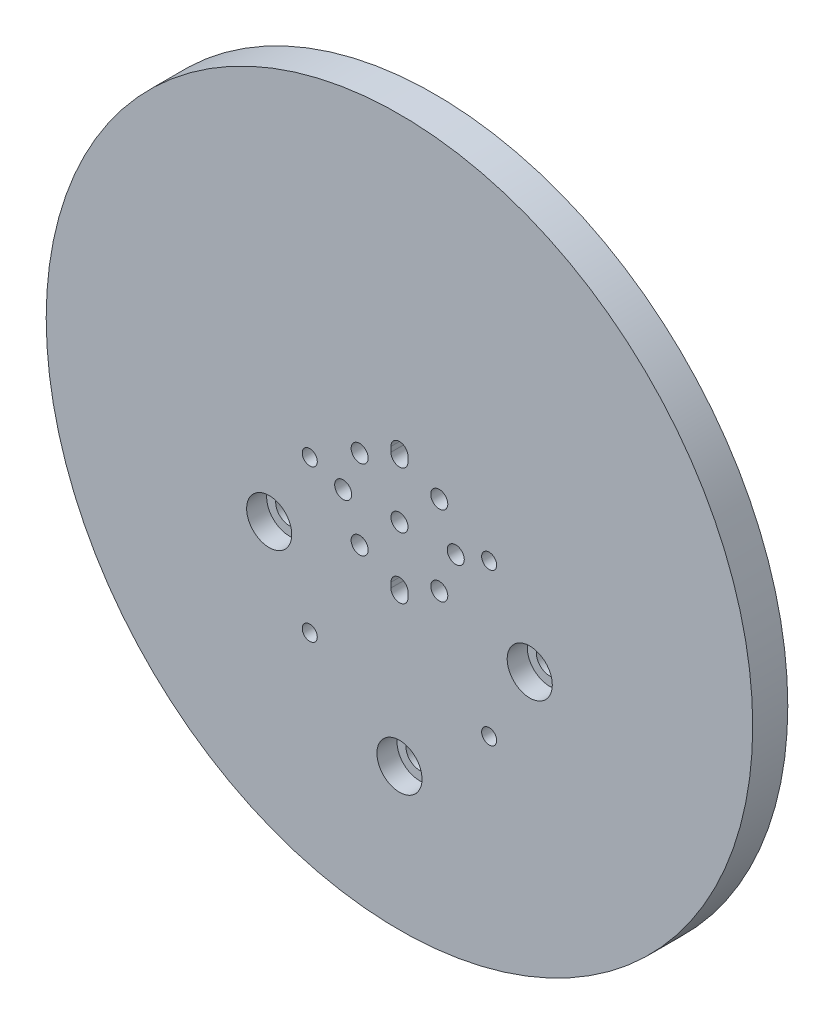
SolidWorks part; units mm, degrees
ref_plane "Front Plane" through (0, 0, 0) normal (0, 0, 1) x (1, 0, 0)
ref_plane "Top Plane" through (0, 0, 0) normal (0, 1, 0) x (1, 0, 0)
ref_plane "Right Plane" through (0, 0, 0) normal (1, 0, 0) x (0, 0, -1)
sketch "Sketch1" plane through (0, 0, 0) normal (0, 0, 1) x (1, 0, 0)
  circle A0 centre (19.5, 0) radius 65.5
  circle A1 centre (26.5, 0) radius 1.7
  circle A2 centre (19.5, -7) radius 1.7
  circle A3 centre (12.5, 0) radius 1.7
  circle A4 centre (19.5, 7) radius 1.7
extrude "Boss-Extrude1" add sketch "Sketch1" along normal blind 7
sketch "Sketch2" plane through (0, 0, 7) normal (0, 0, 1) x (1, 0, 0)
  circle A0 centre (19.5, 0) radius 65.5
  circle A1 centre (19.5, 0) radius 70.5
extrude "Boss-Extrude2" add sketch "Sketch2" against normal blind 7
sketch "Sketch3" plane through (0, 0, 7) normal (0, 0, 1) x (1, 0, 0)
  circle A0 centre (12.5, 0) radius 2.5
  circle A1 centre (19.5, 7) radius 2.5
  circle A2 centre (26.5, 0) radius 2.5
  circle A3 centre (19.5, -7) radius 2.5
sketch "Sketch5" plane through (0, 0, 0) normal (0, 0, -1) x (-1, 0, 0)
  circle A0 centre (-45.5, -12.8987) radius 2.7
  circle A1 centre (6.5, -12.8987) radius 2.7
  circle A2 centre (-19.5, -42.185) radius 2.7
  circle A3 centre (-37.4, 2.2642) radius 1.5
  circle A4 centre (-37.4, -28.0615) radius 1.5
  circle A5 centre (-1.6, -28.0615) radius 1.5
  circle A6 centre (-1.6, 2.2642) radius 1.5
extrude "Cut-Extrude3" cut sketch "Sketch5" against normal blind 15
sketch "Sketch6" plane through (0, 0, 7) normal (0, 0, 1) x (1, 0, 0)
  circle A0 centre (19.5, -42.185) radius 4.5
extrude "Cut-Extrude4" cut sketch "Sketch6" against normal blind 4
sketch "Sketch8" plane through (0, 0, 7) normal (0, 0, 1) x (1, 0, 0)
  circle A0 centre (12.5, 0) radius 1.7
  circle A1 centre (19.5, -7) radius 1.7
  circle A2 centre (26.5, 0) radius 1.7
  circle A3 centre (19.5, 7) radius 1.7
extrude "Boss-Extrude3" add sketch "Sketch8" against normal up to surface (7 mm away) up to face at (42.8, -12.8987, 0)
sketch "Sketch9" plane through (0, 0, 7) normal (0, 0, 1) x (1, 0, 0)
  circle A0 centre (19.5, 11.235) radius 1.7
  circle A1 centre (27.4443, 7.9443) radius 1.7
  circle A2 centre (30.735, 0) radius 1.7
  circle A3 centre (27.4443, -7.9443) radius 1.7
  circle A4 centre (19.5, -11.235) radius 1.7
  circle A5 centre (11.5557, -7.9443) radius 1.7
  circle A6 centre (8.265, 0) radius 1.7
  circle A7 centre (11.5557, 7.9443) radius 1.7
extrude "Cut-Extrude5" cut sketch "Sketch9" against normal blind 14 contours A1 | A0 | A6 | A7 | A5 | A4 | A3 | A2
sketch "Sketch10" plane through (0, 0, 0) normal (0, 0, -1) x (-1, 0, 0)
  circle A0 centre (-19.5, -11.235) radius 2.95
  circle A1 centre (-27.4443, -7.9443) radius 2.95
  circle A2 centre (-30.735, 0) radius 2.95
  circle A3 centre (-27.4443, 7.9443) radius 2.95
  circle A4 centre (-19.5, 11.235) radius 2.95
  circle A5 centre (-11.5557, 7.9443) radius 2.95
  circle A6 centre (-8.265, 0) radius 2.95
  circle A7 centre (-11.5557, -7.9443) radius 2.95
  point P20 (-19.5, 0)
  dimension "D1" = 8
extrude "Cut-Extrude6" cut sketch "Sketch10" against normal blind 2.5
sketch "Sketch11" plane through (0, 0, 7) normal (0, 0, 1) x (1, 0, 0)
  circle A0 centre (19.5, 0) radius 1.7
extrude "Cut-Extrude7" cut sketch "Sketch11" against normal blind 9.5
sketch "Sketch12" plane through (0, 0, 0) normal (0, 0, -1) x (-1, 0, 0)
  circle A0 centre (-19.5, 0) radius 2.95
extrude "Cut-Extrude8" cut sketch "Sketch12" against normal blind 2.5
sketch "Sketch13" plane through (0, 0, 0) normal (0, 0, -1) x (-1, 0, 0)
  line L0 (-19.5, 0) -> (-19.5, 11.235)
  line L1 (-19.5, 11.235) -> (-19.5, 12.235)
  line L2 (-19.5, 0) -> (-19.5, -11.235)
  line L3 (-19.5, -11.235) -> (-19.5, -12.235)
  line L4 (-17.8, -11.235) -> (-17.8, -12.235)
  line L5 (-21.2, -11.235) -> (-21.2, -12.235)
  line L6 (-21.2, -11.235) -> (-17.8, -11.235)
  line L7 (-17.8, 11.235) -> (-17.8, 12.235)
  line L8 (-21.2, 11.235) -> (-21.2, 12.235)
  line L9 (-21.2, 11.235) -> (-17.8, 11.235)
  circle A0 centre (-19.5, -12.235) radius 1.7
  circle A1 centre (-19.5, 12.235) radius 1.7
  circle A2 centre (-19.5, -11.235) radius 1.7 construction
  circle A3 centre (-19.5, 11.235) radius 1.7 construction
  dimension "D3" = 3.4
  dimension "D4" = 3.4
  dimension "D1" = 1
  dimension "D2" = 1
extrude "Cut-Extrude9" cut sketch "Sketch13" against normal blind 10 contours A0 L6 | A0 L4 L6 | A0 L6 L5 | A1 L9 | L9 A1 L0 | L0 A1 L9 | A1 L9 L7 | A1 L8 L9 | L2 A0 L6 | L6 A0 L2 region at (20.0334, 10.9494, 0) region at (18.9666, 10.9494, 0) region at (18.9666, -10.9494, 0) region at (20.0334, -10.9494, 0) region at (19.5, 12.459, 0) region at (21.1043, 11.48, 0) region at (17.8957, 11.48, 0) region at (19.5, -12.459, 0) region at (17.8957, -11.48, 0) region at (21.1043, -11.48, 0)
sketch "Sketch14" plane through (0, 0, 0) normal (0, 0, -1) x (-1, 0, 0)
  line L0 (-19.5, 11.235) -> (-19.5, 12.235) construction
  line L1 (-22.45, 11.235) -> (-22.45, 12.235)
  line L2 (-16.55, 11.235) -> (-16.55, 12.235)
  line L3 (-19.5, -11.235) -> (-19.5, -12.235) construction
  line L4 (-16.55, -11.235) -> (-16.55, -12.235)
  line L5 (-22.45, -11.235) -> (-22.45, -12.235)
  arc A1 (-22.45, 11.235) -> (-16.55, 11.235) centre (-19.5, 11.235) ccw
  arc A2 (-16.55, 12.235) -> (-22.45, 12.235) centre (-19.5, 12.235) ccw
  arc A3 (-16.55, -11.235) -> (-22.45, -11.235) centre (-19.5, -11.235) ccw
  arc A4 (-22.45, -12.235) -> (-16.55, -12.235) centre (-19.5, -12.235) ccw
  point P3 (-19.5, 12.235)
  point P6 (-19.5, 11.735)
  point P15 (-19.5, -11.735)
  dimension "D1" = 2.95
  dimension "D2" = 2.95
extrude "Cut-Extrude11" cut sketch "Sketch14" against normal up to surface (2.5 mm away) contours L2 A2 L1 A1 | L5 A4 L4 A3 up to face at (19.5, -11.735, 2.5)
sketch "Sketch15" plane through (0, 0, 7) normal (0, 0, 1) x (1, 0, 0)
  circle A0 centre (45.5, -12.8987) radius 4.5
  circle A1 centre (-6.5, -12.8987) radius 4.5
  dimension "D1" = 9
extrude "Cut-Extrude12" cut sketch "Sketch15" against normal up to surface (4 mm away) up to face at (24, -42.185, 3)
sketch "Sketch16" plane through (0, 0, 0) normal (0, 0, -1) x (-1, 0, 0)
  line L0 (-19.5, 11.235) -> (-19.5, 12.235) construction
  line L1 (-22.7, 11.235) -> (-22.7, 12.235)
  line L2 (-16.3, 11.235) -> (-16.3, 12.235)
  line L3 (-19.5, -11.235) -> (-19.5, -12.235) construction
  line L4 (-16.3, -11.235) -> (-16.3, -12.235)
  line L5 (-22.7, -11.235) -> (-22.7, -12.235)
  arc A0 (-22.7, 11.235) -> (-16.3, 11.235) centre (-19.5, 11.235) ccw
  arc A1 (-16.3, 12.235) -> (-22.7, 12.235) centre (-19.5, 12.235) ccw
  arc A2 (-16.3, -11.235) -> (-22.7, -11.235) centre (-19.5, -11.235) ccw
  arc A3 (-22.7, -12.235) -> (-16.3, -12.235) centre (-19.5, -12.235) ccw
  point P3 (-19.5, 11.735)
  point P12 (-19.5, -11.735)
  dimension "D2" = 3.2
  dimension "D3" = 3.2
  dimension "D1" = 1
extrude "Cut-Extrude13" cut sketch "Sketch16" against normal up to surface (2.5 mm away) contours L2 A1 L1 A0 | L5 A2 L4 A3 up to face at (16.55, 0, 2.5)
